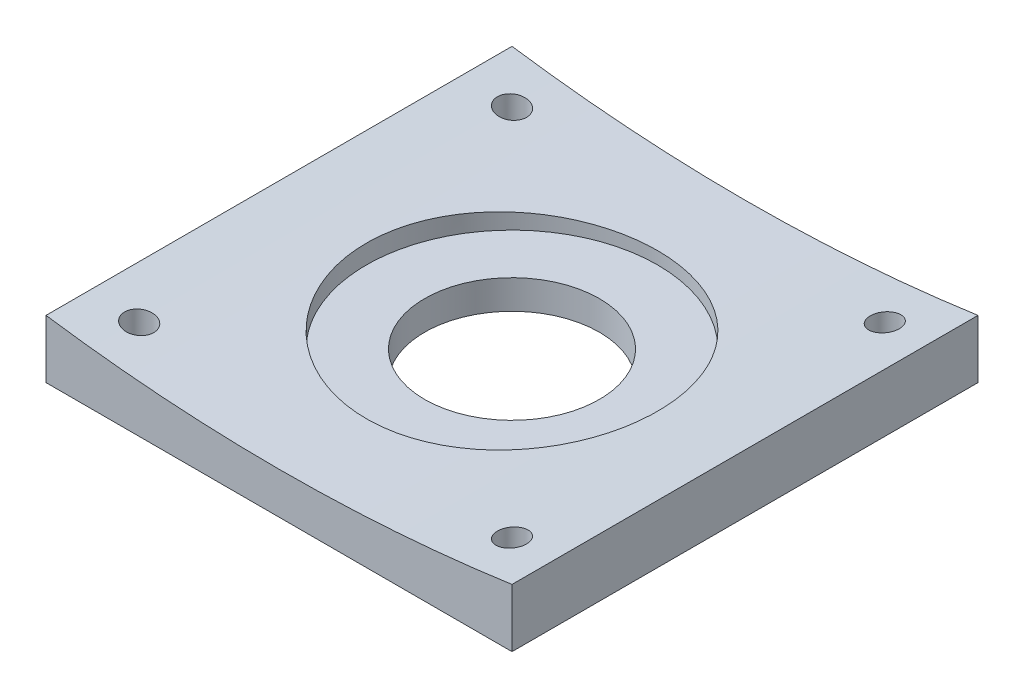
SolidWorks part; units mm, degrees
ref_plane "Front Plane" through (0, 0, 0) normal (0, 0, 1) x (1, 0, 0)
ref_plane "Top Plane" through (0, 0, 0) normal (0, 1, 0) x (1, 0, 0)
ref_plane "Right Plane" through (0, 0, 0) normal (1, 0, 0) x (0, 0, -1)
sketch "Sketch1" plane through (0, 0, 0) normal (0, 1, 0) x (1, 0, 0)
  line L1 (-40, -40) -> (40, -40)
  line L2 (-40, -40) -> (-40, 40)
  line L3 (-40, 40) -> (40, 40)
  line L4 (40, -40) -> (40, 40)
  line L5 (-40, -40) -> (40, 40) construction
  line L6 (-40, 40) -> (40, -40) construction
  circle A0 centre (0, 0) radius 15
  circle A1 centre (0, 0) radius 25
  circle A2 centre (-32, 32) radius 2.5
  circle A3 centre (-32, -32) radius 2.5
  circle A4 centre (32, -32) radius 2.5
  circle A5 centre (32, 32) radius 2.5
  point P19 (0, 0)
  dimension "D1" = 50
  dimension "D2" = 30
  dimension "D4" = 5
  dimension "D3" = 80
  dimension "D5" = 8
  dimension "D6" = 4
extrude "Boss-Extrude3" add sketch "Sketch1<3>" against normal blind 5 contours L1 L4 L3 L2 A1 | A1 A0 region at (-38.8686, 0, 0) region at (-24.2929, 0, 0)
sketch "Sketch1<3>" plane through (0, 0, 0) normal (0, 1, 0) x (1, 0, 0) same geometry as "Sketch1"
extrude "Boss-Extrude4" add sketch "Sketch1" along normal blind 5 contours L1 L4 L3 L2 A1 region at (-38.8686, 0, 0)
sketch "Sketch5" plane through (0, 0, -40) normal (0, 0, -1) x (-1, 0, 0)
  line L0 (40, 5) -> (-40, 5)
  arc A0 (40, 5) -> (-40, 5) centre (0, 282.1281) cw
  dimension "D1" = 280
extrude "Cut-Extrude1" cut sketch "Sketch5" against normal through all
